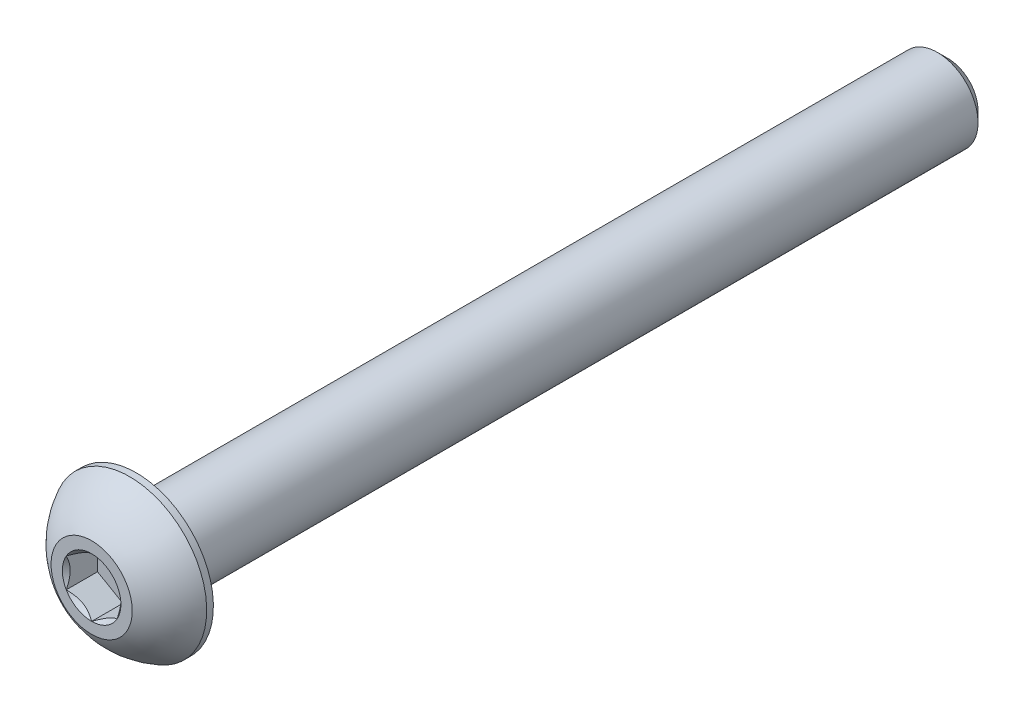
SolidWorks part; units mm, degrees
ref_plane "Front" through (0, 0, 0) normal (0, 0, 1) x (1, 0, 0)
ref_plane "Top" through (0, 0, 0) normal (0, 1, 0) x (1, 0, 0)
ref_plane "Right" through (0, 0, 0) normal (1, 0, 0) x (0, 0, -1)
sketch "Sketch1" plane through (0, 0, 0) normal (1, 0, 0) x (0, 0, -1)
  line L2 (-20, 2) -> (20, 2)
  line L3 (20, 2) -> (20, 0)
  line L4 (20, 0) -> (-20, 0)
  line L6 (-20.33, 3.8) -> (-20, 3.8) construction
  line L7 (20, 2) -> (20, -2) construction
  line L8 (-22.2, 0) -> (-20, 0) construction
  line L9 (-20, 3.8) -> (-20, -3.8) construction
  line L11 (-20, 2) -> (-20, 0)
  line L13 (-22.2, 1.25) -> (-22.2, -1.25) construction
  line L14 (-22.2, 1.25) -> (-22.2, 2) construction
  line L15 (20, 2) -> (20.6125, 2)
  line L16 (20.6125, 2) -> (20.35, 1.5453)
  line L17 (20, 2) -> (19.3, 2) construction
  line L18 (20.35, 1.5453) -> (20.2625, 1.5453)
  line L19 (20.2625, 1.5453) -> (20, 2)
  line L20 (20.3063, 2) -> (20.3063, 1.5453) construction
  line L21 (20.1313, 1.7727) -> (20.4813, 1.7727) construction
  line L26 (19.475, 2) -> (20, 1.475)
  arc A3 (-22.2, 2) -> (-20.33, 3.8) centre (-18.4736, 0) cw construction
  point P30 (18.25, -2)
  point P32 (20, 2)
  point P33 (15, 0)
  point P34 (0, 0)
  point P35 (-15, 0)
  dimension "Thread Size" = 4
  dimension "D1" = 0.33
  dimension "Head Height" = 2.2
  dimension "Head Diameter" = 7.6
  dimension "Length" = 40
  dimension "Drive Size" = 2.5
  dimension "Thread Pitch" = 0.7
  dimension "D2" = 0.525
  dimension "D4" = 45
  dimension "D5" = 1.75
  dimension "D6" = 5
  dimension "D7" = 5
  dimension "D3" = 0.0875
  dimension "D8" = 0.35
  dimension "D9" = 60
sketch "Sketch10" plane through (0, 0, 0) normal (1, 0, 0) x (0, 0, -1)
  line L2 (-20, 2) -> (-20, 0)
  line L3 (-20, 0) -> (20, 0)
  line L4 (20, 0) -> (20, 1.475)
  line L5 (20, 1.475) -> (19.475, 2)
  line L6 (19.475, 2) -> (-20, 2)
revolve "Revolve3" add sketch "Sketch10" angle 360 about L8
sketch "Sketch7" plane through (0, 0, 0) normal (1, 0, 0) x (0, 0, -1)
  line L6 (-20.33, 3.8) -> (-20, 3.8) construction
  line L8 (-22.2, 0) -> (-20, 0) construction
  line L11 (-20, 3.8) -> (-20, -3.8) construction
  line L12 (-20.33, 3.8) -> (-20, 3.8)
  line L13 (-22.2, 0) -> (-20, 0)
  line L14 (-22.2, 1.25) -> (-22.2, -1.25) construction
  line L15 (-20, 3.8) -> (-20, 0)
  line L16 (-22.2, 2) -> (-22.2, 0)
  arc A2 (-20.33, 3.8) -> (-22.2, 2) centre (-18.4736, 0) ccw construction
  arc A3 (-20.33, 3.8) -> (-22.2, 2) centre (-18.4736, 0) ccw
revolve "Revolve2" add sketch "Sketch7" angle 360 mid plane about L13
sketch "Sketch5" plane through (0, 0, 22.2) normal (0, 0, 1) x (1, 0, 0)
  line L1 (1.25, -0.7217) -> (1.25, 0.7217)
  line L2 (1.25, 0.7217) -> (0, 1.4434)
  line L3 (0, 1.4434) -> (-1.25, 0.7217)
  line L4 (-1.25, 0.7217) -> (-1.25, -0.7217)
  line L5 (-1.25, -0.7217) -> (0, -1.4434)
  line L6 (0, -1.4434) -> (1.25, -0.7217)
  circle A0 centre (0, 0) radius 1.25 construction
extrude "Cut-Extrude2" cut sketch "Sketch5" against normal blind 1.54
sketch "Sketch6" plane through (0, 0, 22.2) normal (0, 0, 1) x (1, 0, 0)
  circle A0 centre (0, 0) radius 1.4434
extrude "Cut-Extrude3" cut sketch "Sketch6" against normal blind 1.54 draft 45
sketch "Sketch9" [suppressed] plane through (0, 0, 20) normal (0, 0, -1) x (-1, 0, 0)
  circle A4 centre (0, 0) radius 2
split "Split1" [suppressed] bodies to split 113
sketch "Sketch13" [suppressed] plane through (0, 0, 0) normal (1, 0, 0) x (0, 0, -1)
  line L0 (19.475, 2) -> (20, 2)
  line L1 (20, 2) -> (20, 0)
  line L3 (20, 0) -> (19.475, 0)
  line L5 (19.475, 0) -> (19.475, 2)
revolve "Revolve4" [suppressed] add sketch "Sketch13" angle 360 about L3
sketch "Sketch11" [suppressed] plane through (0, 0, -20) normal (0, 0, -1) x (-1, 0, 0)
  circle A1 centre (0, 0) radius 2
curve "Helix/Spiral1" [suppressed] pitch 0.7 height 7 turns 10
sketch "Sketch12" [suppressed] plane through (0, 0, 0) normal (1, 0, 0) x (0, 0, -1)
  line L8 (20, 2) -> (20.6125, 2)
  line L9 (20.6125, 2) -> (20.35, 1.5453)
  line L10 (20.35, 1.5453) -> (20.2625, 1.5453)
  line L11 (20.2625, 1.5453) -> (20, 2)
sweep "Cut-Sweep2" [suppressed] cut profiles "Sketch12" path "Helix/Spiral1"
pattern_linear "LPattern1" [suppressed] count 6 spacing 7 of bodies 132
sketch "Sketch14" [suppressed] plane through (0, 0, 0) normal (1, 0, 0) x (0, 0, -1)
  line L0 (19.475, 2) -> (20, 2)
  line L1 (20, 2) -> (20, 1.475)
  line L2 (20, 1.475) -> (19.475, 2)
  line L3 (20, 0) -> (-22.2, 0) construction
revolve "Cut-Revolve1" [suppressed] cut sketch "Sketch14" angle 360 about L3
extrude "Boss-Extrude1" [suppressed] add sketch "Sketch9" along normal blind 10 draft 45
equation "\"D1@Cut-Extrude2\" = \"Head Height@Sketch1\" * .7"
equation "\"D1@Sketch1\" = \"Head Height@Sketch1\" * .15"
equation "\"D1@Cut-Extrude3\" = \"D1@Cut-Extrude2\""
equation "\"D3@Sketch1\"=\"Thread Pitch@Sketch1\" / 8"
equation "\"D2@Sketch1\" = \"Thread Pitch@Sketch1\" * 0.75"
equation "\"D3@Helix/Spiral1\"= \"Thread Pitch@Sketch1\"*10"
equation "\"D4@Helix/Spiral1\" = \"Thread Pitch@Sketch1\""
equation "\"D5@Sketch1\" = \"Thread Pitch@Sketch1\" * 2.5"
equation "\"D3@LPattern1\"=(\"Thread Pitch@Sketch1\" ) *10"
equation "\"D8@Sketch1\" = \"Thread Pitch@Sketch1\" * .5"
equation "\"D1@LPattern1\" = INT (  ( \"Length@Sketch1\" )  /  ( \"Thread Pitch@Sketch1\" * 10 )  )  + 1"
equation "\"D7@Sketch1\"=\"D6@Sketch1\""
equation "\"D6@Sketch1\" = \"Length@Sketch1\" * .125"
